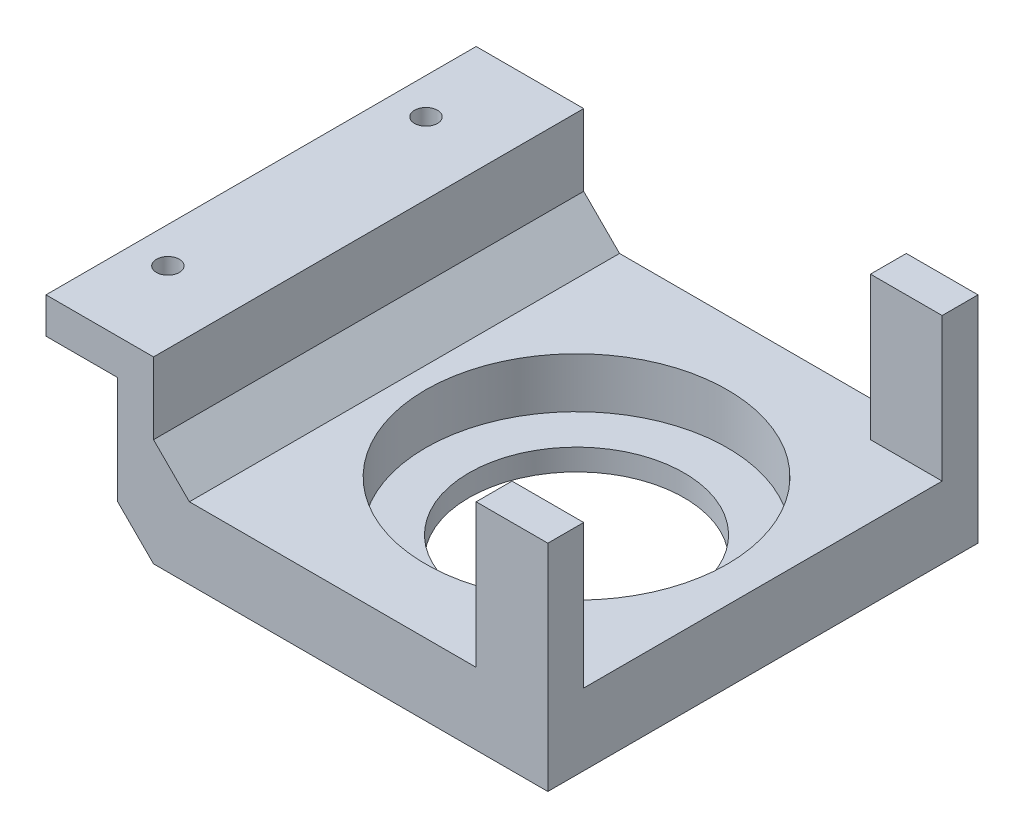
SolidWorks part; units mm, degrees
ref_plane "Alzado" through (0, 0, 0) normal (0, 0, 1) x (1, 0, 0)
ref_plane "Planta" through (0, 0, 0) normal (0, 1, 0) x (1, 0, 0)
ref_plane "Vista lateral" through (0, 0, 0) normal (1, 0, 0) x (0, 0, -1)
sketch "Croquis4" plane through (0, 0, 0) normal (0, 0, 1) x (1, 0, 0)
  line L0 (-31.4286, 5.7619) -> (-31.4286, 14.7619)
  line L5 (-26.4286, 4.7619) -> (28.5714, 4.7619)
  line L6 (-31.4286, 5.7619) -> (-31.4286, -5.2381)
  line L7 (-31.4286, -5.2381) -> (28.5714, -5.2381)
  line L8 (28.5714, 4.7619) -> (28.5714, -5.2381)
  line L9 (-31.4286, 5.7619) -> (28.5714, -5.2381) construction
  line L10 (-31.4286, -5.2381) -> (28.5714, 4.7619) construction
  line L11 (-31.4286, 14.7619) -> (-41.4286, 14.7619)
  line L12 (-41.4286, 14.7619) -> (-41.4286, 19.7619)
  line L13 (-41.4286, 19.7619) -> (-26.4286, 19.7619)
  line L14 (-26.4286, 19.7619) -> (-26.4286, 4.7619)
  point P0 (0, 0)
  dimension "D1" = 11
  dimension "D2" = 60
  dimension "D3" = 5
  dimension "D4" = 5
  dimension "D5" = 10
  dimension "D6" = 10
  dimension "D7" = 15
extrude "Saliente-Extruir2" add sketch "Croquis4" along normal blind 60
sketch "Croquis6" plane through (0, 4.7619, 0) normal (0, 1, 0) x (1, 0, 0)
  line L1 (28.5714, -60) -> (28.5714, 0) construction
  line L2 (28.5714, -30) -> (-26.4286, -30) construction
  line L3 (-26.4286, -60) -> (-26.4286, 0) construction
  circle A0 centre (2.5714, -30) radius 21.05
  point P8 (2.5714, -30)
  dimension "D1" = 42.1
  dimension "D3" = 26
extrude "Cortar-Extruir1" cut sketch "Croquis6" against normal blind 7
sketch "Croquis8" plane through (0, -2.2381, 0) normal (0, 1, 0) x (1, 0, 0)
  circle A0 centre (2.5714, -30) radius 15
  dimension "D1" = 30
extrude "Cortar-Extruir2" cut sketch "Croquis8" against normal through all both and the other way through all
sketch "Croquis9" plane through (0, 14.7619, 0) normal (0, -1, 0) x (1, 0, 0)
  line L0 (-41.4286, 30) -> (-31.4286, 30) construction
  line L1 (-41.4286, 60) -> (-41.4286, 0) construction
  line L2 (-31.4286, 60) -> (-31.4286, 0) construction
  line L3 (-36.4286, 30) -> (-36.4286, 61.1151) construction
  circle A0 centre (-36.4286, 48) radius 1.6
  circle A2 centre (-36.4286, 12) radius 1.6
  dimension "D1" = 18
  dimension "D2" = 3.2
extrude "Cortar-Extruir3" cut sketch "Croquis9" against normal through all both and the other way through all
chamfer "Chaflán1" distance 5 angle 45 2 edges at (-26.4286, 4.7619, 30) (-31.4286, -5.2381, 30)
sketch "Croquis11" plane through (0, 4.7619, 0) normal (0, 1, 0) x (1, 0, 0)
  line L0 (28.5714, 0) -> (28.5714, -5)
  line L1 (28.5714, -60) -> (28.5714, 0) construction
  line L2 (28.5714, -5) -> (18.5714, -5)
  line L3 (18.5714, -5) -> (18.5714, 0)
  line L4 (28.5714, 0) -> (-21.4286, 0) construction
  line L5 (18.5714, 0) -> (28.5714, 0)
  line L6 (28.5714, -30) -> (-21.4286, -30) construction
  line L7 (-21.4286, 0) -> (-21.4286, -60) construction
  line L8 (18.5714, -60) -> (28.5714, -60)
  line L9 (18.5714, -55) -> (18.5714, -60)
  line L10 (28.5714, -55) -> (18.5714, -55)
  line L11 (28.5714, -60) -> (28.5714, -55)
  dimension "D1" = 10
  dimension "D2" = 5
extrude "Saliente-Extruir3" add sketch "Croquis11" along normal blind 20
